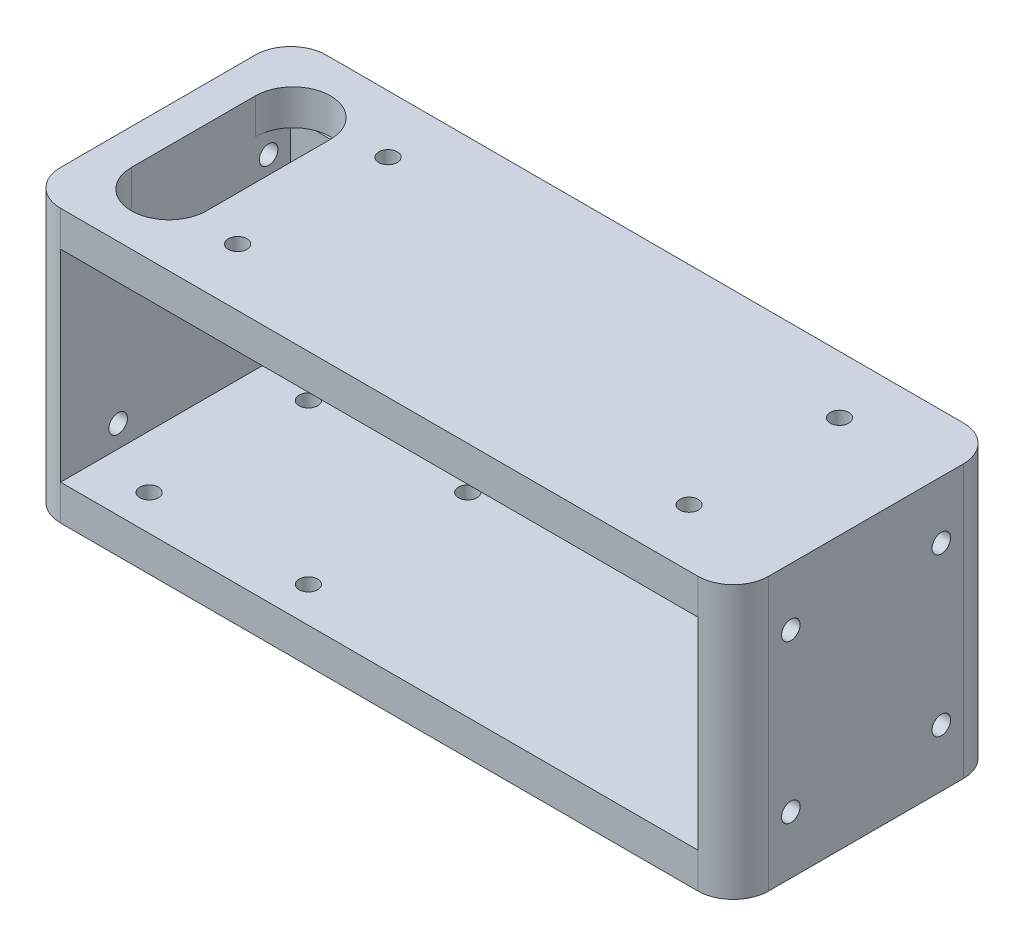
SolidWorks part; units mm, degrees
ref_plane "前视基准面" through (0, 0, 0) normal (0, 0, 1) x (1, 0, 0)
ref_plane "上视基准面" through (0, 0, 0) normal (0, 1, 0) x (1, 0, 0)
ref_plane "右视基准面" through (0, 0, 0) normal (1, 0, 0) x (0, 0, -1)
other "Configuration Table"
sketch "草图1" plane through (0, 0, 0) normal (0, 1, 0) x (1, 0, 0)
  line L1 (80, -30) -> (-80, -30)
  line L2 (80, -30) -> (80, 30)
  line L3 (80, 30) -> (-80, 30)
  line L4 (-80, -30) -> (-80, 30)
  line L5 (80, -30) -> (-80, 30) construction
  line L6 (80, 30) -> (-80, -30) construction
  point P0 (0, 0)
  dimension "D1" = 60
  dimension "D2" = 160
extrude "凸台-拉伸1" add sketch "草图1" along normal blind 61.6
sketch "草图3" plane through (0, 0, 30) normal (0, 0, 1) x (1, 0, 0)
  line L0 (-80, 0) -> (80, 0) construction
  line L1 (72, 8) -> (-72, 8)
  line L2 (72, 8) -> (72, 53.6)
  line L3 (72, 53.6) -> (-72, 53.6)
  line L4 (-72, 8) -> (-72, 53.6)
  line L5 (72, 8) -> (-72, 53.6) construction
  line L6 (72, 53.6) -> (-72, 8) construction
  line L7 (-80, 61.6) -> (-80, 0) construction
  line L8 (80, 61.6) -> (80, 0) construction
  line L9 (-80, 61.6) -> (80, 61.6) construction
  point P0 (0, 30.8)
  dimension "D1" = 8
  dimension "D2" = 8
  dimension "D3" = 8
  dimension "D4" = 8
extrude "切除-拉伸1" cut sketch "草图3" against normal blind 52
fillet "圆角1" radius 8 4 edges at (-80, 30.8, -30) (80, 30.8, -30) (80, 30.8, 30) (-80, 30.8, 30)
sketch "草图4" plane through (-80, 0, 0) normal (-1, 0, 0) x (0, 0, 1)
  line L5 (-22, 61.6) -> (22, 61.6) construction
  line L9 (17, 13) -> (-17, 13) construction
  line L10 (17, 13) -> (17, 48.6) construction
  line L11 (17, 48.6) -> (-17, 48.6) construction
  line L13 (-17, 13) -> (-17, 48.6) construction
  line L14 (17, 13) -> (-17, 48.6) construction
  line L15 (17, 48.6) -> (-17, 13) construction
  line L18 (30, 53.6) -> (30, 8) construction
  line L19 (-30, 0) -> (-30, 61.6) construction
  line L21 (30, 0) -> (-30, 0) construction
  line L22 (-17, 30.8) -> (17, 30.8) construction
  line L23 (0, 48.6) -> (0, 13) construction
  circle A8 centre (-17, 48.6) radius 2.1
  circle A9 centre (17, 48.6) radius 2.1
  circle A10 centre (17, 13) radius 2.1
  circle A11 centre (-17, 13) radius 2.1
  point P0 (0, 30.8)
  dimension "D5" = 4.2
  dimension "D1" = 13
  dimension "D2" = 13
  dimension "D3" = 13
  dimension "D4" = 13
extrude "切除-拉伸2" cut sketch "草图4" against normal through all
sketch "草图5" plane through (0, 8, 0) normal (0, 1, 0) x (1, 0, 0)
  line L0 (-80, -30) -> (-80, 30) construction
  line L1 (-24, -22) -> (-60, -22) construction
  line L2 (-24, -22) -> (-24, 14) construction
  line L3 (-24, 14) -> (-60, 14) construction
  line L4 (-60, -22) -> (-60, 14) construction
  line L5 (-24, -22) -> (-60, 14) construction
  line L6 (-24, 14) -> (-60, -22) construction
  line L8 (-60, -4) -> (-24, -4) construction
  line L9 (-42, -22) -> (-42, 14) construction
  line L10 (80, 30) -> (-80, 30) construction
  circle A0 centre (-60, 14) radius 2.1
  circle A1 centre (-24, 14) radius 2.1
  circle A2 centre (-24, -22) radius 2.1
  circle A3 centre (-60, -22) radius 2.1
  point P0 (-42, -4)
  dimension "D4" = 4.2
  dimension "D1" = 20
  dimension "D2" = 36
  dimension "D3" = 36
  dimension "D5" = 16
extrude "切除-拉伸3" cut sketch "草图5" against normal through all
sketch "草图6" plane through (0, 61.6, 0) normal (0, 1, 0) x (1, 0, 0)
  line L0 (80, -22) -> (80, 22) construction
  line L1 (57, -17) -> (-45, -17) construction
  line L2 (57, -17) -> (57, 17) construction
  line L3 (57, 17) -> (-45, 17) construction
  line L4 (-45, -17) -> (-45, 17) construction
  line L5 (57, -17) -> (-45, 17) construction
  line L6 (57, 17) -> (-45, -17) construction
  line L7 (-72, -30) -> (72, -30) construction
  line L8 (6, 17) -> (6, -17) construction
  line L9 (-45, 0) -> (57, 0) construction
  line L11 (-63.5, -14) -> (-63.5, 14) construction
  line L12 (-72, -14) -> (-72, 14)
  line L13 (-55, -14) -> (-55, 14)
  line L14 (-80, 22) -> (-80, -22) construction
  line L15 (72, 30) -> (-72, 30) construction
  circle A0 centre (-45, 17) radius 2.1
  circle A1 centre (57, 17) radius 2.1
  circle A2 centre (57, -17) radius 2.1
  circle A3 centre (-45, -17) radius 2.1
  arc A4 (-72, -14) -> (-55, -14) centre (-63.5, -14) ccw
  arc A5 (-55, 14) -> (-72, 14) centre (-63.5, 14) ccw
  point P0 (6, 0)
  point P20 (-63.5, 0)
  dimension "D4" = 4.2
  dimension "D1" = 23
  dimension "D2" = 13
  dimension "D3" = 102
  dimension "D5" = 8
  dimension "D6" = 17
  dimension "D7" = 16
  dimension "D8" = 16
extrude "切除-拉伸4" cut sketch "草图6" against normal up to surface (8 mm away) up to face at (0, 53.6, 4)
